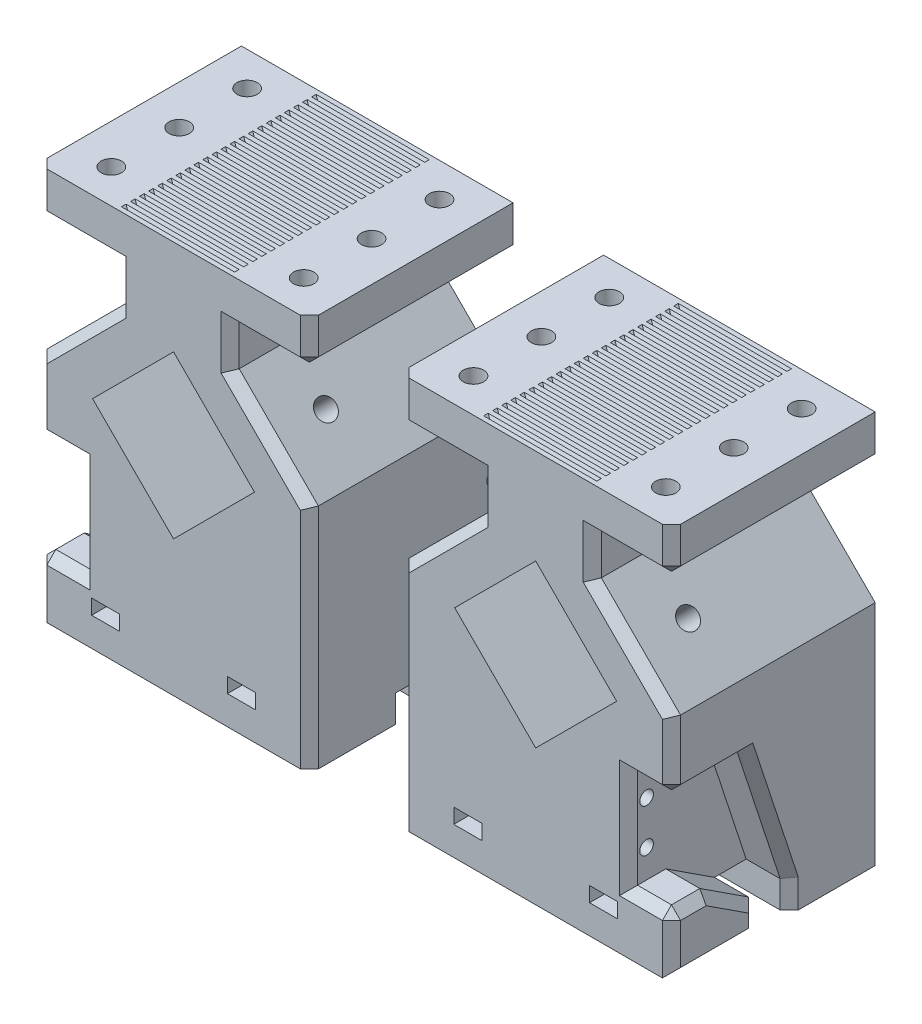
SolidWorks part; units mm, degrees
material "ABS"
ref_plane "Front Plane" through (0, 0, 0) normal (0, 0, 1) x (1, 0, 0)
ref_plane "Top Plane" through (0, 0, 0) normal (0, 1, 0) x (1, 0, 0)
ref_plane "Right Plane" through (0, 0, 0) normal (1, 0, 0) x (0, 0, -1)
sketch "Sketch1" plane through (0, 0, 0) normal (0, 0, 1) x (1, 0, 0)
  line L0 (-30, 25.15) -> (-12.5, 42.65)
  line L2 (30, 25.15) -> (30, -25.15)
  line L3 (30, -25.15) -> (-30, -25.15)
  line L4 (-30, 25.15) -> (-30, -25.15)
  line L5 (30, 25.15) -> (-30, -25.15) construction
  line L6 (30, -25.15) -> (-30, 25.15) construction
  line L7 (30, 25.15) -> (12.5, 42.65)
  line L8 (12.5, 42.65) -> (12.5, 51.65)
  line L9 (-12.5, 42.65) -> (-12.5, 51.65)
  line L10 (-12.5, 51.65) -> (12.5, 51.65) construction
  line L11 (-12.5, 51.65) -> (-30, 51.65)
  line L12 (-30, 51.65) -> (-30, 61.65)
  line L13 (-30, 61.65) -> (30, 61.65)
  line L14 (30, 61.65) -> (30, 51.65)
  line L15 (30, 51.65) -> (12.5, 51.65)
  point P0 (0, 0)
  dimension "D1" = 60
  dimension "D2" = 50.3
  dimension "D3" = 17.5
  dimension "D4" = 17.5
  dimension "D5" = 17.5
  dimension "D6" = 17.5
  dimension "D7" = 9
  dimension "D8" = 10
  dimension "D9" = 25.15
extrude "Boss-Extrude1" add sketch "Sketch1" along normal blind 45
sketch "Sketch2" plane through (0, 0, 45) normal (0, 0, 1) x (1, 0, 0)
  line L0 (0, 40.6296) -> (-17.8898, 22.7398)
  line L1 (-17.8898, 22.7398) -> (0, 4.85)
  line L2 (0, 4.85) -> (17.8898, 22.7398)
  line L3 (17.8898, 22.7398) -> (0, 40.6296)
  line L4 (0, 40.6296) -> (0, 0) construction
  line L5 (-30, -25.15) -> (30, -25.15) construction
  dimension "D1" = 25.3
  dimension "D2" = 25.3
  dimension "D3" = 30
extrude "Cut-Extrude1" cut sketch "Sketch2" against normal blind 25
sketch "Sketch3" plane through (0, -25.15, 0) normal (0, -1, 0) x (1, 0, 0)
  line L0 (-30, 26) -> (30, 26)
  line L1 (-30, 45) -> (-30, 0) construction
  line L2 (30, 45) -> (30, 0) construction
  line L3 (30, 26) -> (30, 19)
  line L4 (30, 19) -> (4.5, 19)
  line L5 (4.5, 19) -> (4.5, 3)
  line L6 (4.5, 3) -> (-4.5, 3)
  line L7 (-4.5, 3) -> (-4.5, 19)
  line L8 (-4.5, 19) -> (-30, 19)
  line L9 (-30, 19) -> (-30, 26)
  line L10 (0, 0) -> (0, 45) construction
  line L11 (-30, 0) -> (30, 0) construction
  line L12 (-30, 45) -> (30, 45) construction
  point P17 (0, 3)
  dimension "D1" = 9
  dimension "D2" = 7
  dimension "D3" = 16
  dimension "D4" = 19
extrude "Cut-Extrude2" cut sketch "Sketch3" against normal blind 6
sketch "Sketch4" plane through (-30, 0, 0) normal (-1, 0, 0) x (0, 0, 1)
  line L0 (45, 25.15) -> (45, -25.15) construction
  line L1 (45, 9.85) -> (28.5, 9.85)
  line L2 (45, 9.85) -> (45, -12.15)
  line L3 (45, -12.15) -> (36.75, -12.15)
  line L5 (45, -25.15) -> (26, -25.15) construction
  line L6 (26, -19.15) -> (36.75, -12.15)
  line L7 (19, -19.15) -> (28.5, 9.85)
  line L8 (26, -19.15) -> (19, -19.15)
  dimension "D1" = 16.5
  dimension "D2" = 13
  dimension "D3" = 22
  dimension "D4" = 8.25
extrude "Cut-Extrude4" cut sketch "Sketch4" against normal blind 9.5
sketch "Sketch5" plane through (0, 0, 0) normal (1, 0, 0) x (0, 0, -1)
  line L0 (-3, -19.15) -> (-3, 9.5665)
  line L1 (-4.0851, 13.008) -> (-11.2085, 23.1813)
  line L2 (-16.1234, 25.7398) -> (-20, 25.7398)
  line L3 (-20, 40.6296) -> (-20, 22.7398) construction
  line L4 (-20, 25.7398) -> (-20, 19.7398)
  line L5 (-20, 22.7398) -> (-20, 4.85) construction
  line L6 (-20, 19.7398) -> (-19.2468, 19.7398)
  line L7 (-14.3319, 17.1813) -> (-10.0851, 11.1162)
  line L8 (-9, 7.6747) -> (-9, -19.15)
  line L9 (-19, -19.15) -> (-3, -19.15) construction
  line L10 (-9, -19.15) -> (-3, -19.15)
  line L11 (-20, 22.7398) -> (-45, 22.7398) construction
  arc A0 (-3, 9.5665) -> (-4.0851, 13.008) centre (-9, 9.5665) ccw
  arc A1 (-10.0851, 11.1162) -> (-9, 7.6747) centre (-15, 7.6747) cw
  arc A2 (-11.2085, 23.1813) -> (-16.1234, 25.7398) centre (-16.1234, 19.7398) ccw
  arc A3 (-19.2468, 19.7398) -> (-14.3319, 17.1813) centre (-19.2468, 13.7398) cw
  point P15 (-19.6234, 19.7398)
  point P24 (-13, 25.7398)
  dimension "D7" = 6
  dimension "D1" = 6
  dimension "D2" = 6
  dimension "D3" = 6
  dimension "D4" = 3
  dimension "D5" = 145
  dimension "D6" = 7
extrude "Cut-Extrude5" cut sketch "Sketch5" against normal mid plane 9
fillet "Fillet1" radius 6 1 edges at (0, -19.15, 9)
ref_plane "Plane1" through (11.5, 0, 0) normal (1, 0, 0) x (0, 0, -1)
sketch "Sketch7" plane through (11.5, 0, 0) normal (1, 0, 0) x (0, 0, -1)
  line L0 (-1, 61.65) -> (-2, 61.65)
  line L1 (-45, 61.65) -> (0, 61.65) construction
  line L2 (-2, 61.65) -> (-1.5, 60.65)
  line L3 (-1.5, 60.65) -> (-1, 61.65)
  line L4 (-1.5, 60.65) -> (-1.5, 61.65) construction
  line L5 (-4, 61.65) -> (-3.5, 60.65)
  line L6 (-3, 61.65) -> (-4, 61.65)
  line L7 (-3.5, 60.65) -> (-3, 61.65)
  line L8 (-6, 61.65) -> (-5.5, 60.65)
  line L9 (-5, 61.65) -> (-6, 61.65)
  line L10 (-5.5, 60.65) -> (-5, 61.65)
  line L11 (-8, 61.65) -> (-7.5, 60.65)
  line L12 (-7, 61.65) -> (-8, 61.65)
  line L13 (-7.5, 60.65) -> (-7, 61.65)
  line L14 (-10, 61.65) -> (-9.5, 60.65)
  line L15 (-9, 61.65) -> (-10, 61.65)
  line L16 (-9.5, 60.65) -> (-9, 61.65)
  line L17 (-12, 61.65) -> (-11.5, 60.65)
  line L18 (-11, 61.65) -> (-12, 61.65)
  line L19 (-11.5, 60.65) -> (-11, 61.65)
  line L20 (-14, 61.65) -> (-13.5, 60.65)
  line L21 (-13, 61.65) -> (-14, 61.65)
  line L22 (-13.5, 60.65) -> (-13, 61.65)
  line L23 (-16, 61.65) -> (-15.5, 60.65)
  line L24 (-15, 61.65) -> (-16, 61.65)
  line L25 (-15.5, 60.65) -> (-15, 61.65)
  line L26 (-18, 61.65) -> (-17.5, 60.65)
  line L27 (-17, 61.65) -> (-18, 61.65)
  line L28 (-17.5, 60.65) -> (-17, 61.65)
  line L29 (-20, 61.65) -> (-19.5, 60.65)
  line L30 (-19, 61.65) -> (-20, 61.65)
  line L31 (-19.5, 60.65) -> (-19, 61.65)
  line L32 (-22, 61.65) -> (-21.5, 60.65)
  line L33 (-21, 61.65) -> (-22, 61.65)
  line L34 (-21.5, 60.65) -> (-21, 61.65)
  line L35 (-24, 61.65) -> (-23.5, 60.65)
  line L36 (-23, 61.65) -> (-24, 61.65)
  line L37 (-23.5, 60.65) -> (-23, 61.65)
  line L38 (-26, 61.65) -> (-25.5, 60.65)
  line L39 (-25, 61.65) -> (-26, 61.65)
  line L40 (-25.5, 60.65) -> (-25, 61.65)
  line L41 (-28, 61.65) -> (-27.5, 60.65)
  line L42 (-27, 61.65) -> (-28, 61.65)
  line L43 (-27.5, 60.65) -> (-27, 61.65)
  line L44 (-30, 61.65) -> (-29.5, 60.65)
  line L45 (-29, 61.65) -> (-30, 61.65)
  line L46 (-29.5, 60.65) -> (-29, 61.65)
  line L47 (-32, 61.65) -> (-31.5, 60.65)
  line L48 (-31, 61.65) -> (-32, 61.65)
  line L49 (-31.5, 60.65) -> (-31, 61.65)
  line L50 (-34, 61.65) -> (-33.5, 60.65)
  line L51 (-33, 61.65) -> (-34, 61.65)
  line L52 (-33.5, 60.65) -> (-33, 61.65)
  line L53 (-36, 61.65) -> (-35.5, 60.65)
  line L54 (-35, 61.65) -> (-36, 61.65)
  line L55 (-35.5, 60.65) -> (-35, 61.65)
  line L56 (-38, 61.65) -> (-37.5, 60.65)
  line L57 (-37, 61.65) -> (-38, 61.65)
  line L58 (-37.5, 60.65) -> (-37, 61.65)
  line L59 (-40, 61.65) -> (-39.5, 60.65)
  line L60 (-39, 61.65) -> (-40, 61.65)
  line L61 (-39.5, 60.65) -> (-39, 61.65)
  line L62 (-42, 61.65) -> (-41.5, 60.65)
  line L63 (-41, 61.65) -> (-42, 61.65)
  line L64 (-41.5, 60.65) -> (-41, 61.65)
  line L65 (-44, 61.65) -> (-43.5, 60.65)
  line L66 (-43, 61.65) -> (-44, 61.65)
  line L67 (-43.5, 60.65) -> (-43, 61.65)
  dimension "D1" = 1
  dimension "D2" = 1
  dimension "D3" = 1
  dimension "D4" = 22
extrude "Cut-Extrude7" cut sketch "Sketch7" against normal blind 23
chamfer "Chamfer1" distance 1 angle 45 44 edges at (-11.5, 61.65, 43.5) (-11.5, 61.65, 41.5) (-11.5, 61.65, 39.5) (-11.5, 61.65, 37.5) (-11.5, 61.65, 35.5) (-11.5, 61.65, 33.5) (-11.5, 61.65, 31.5) (-11.5, 61.65, 29.5) (-11.5, 61.65, 27.5) (-11.5, 61.65, 25.5) (-11.5, 61.65, 23.5) (-11.5, 61.65, 21.5) (-11.5, 61.65, 19.5) (-11.5, 61.65, 17.5) (-11.5, 61.65, 15.5) (-11.5, 61.65, 13.5) (-11.5, 61.65, 11.5) (-11.5, 61.65, 9.5) (-11.5, 61.65, 7.5) (-11.5, 61.65, 5.5) (-11.5, 61.65, 3.5) (-11.5, 61.65, 1.5) (11.5, 61.65, 43.5) (11.5, 61.65, 41.5) (11.5, 61.65, 39.5) (11.5, 61.65, 37.5) (11.5, 61.65, 35.5) (11.5, 61.65, 33.5) (11.5, 61.65, 31.5) (11.5, 61.65, 29.5) (11.5, 61.65, 27.5) (11.5, 61.65, 25.5) (11.5, 61.65, 23.5) (11.5, 61.65, 21.5) (11.5, 61.65, 19.5) (11.5, 61.65, 17.5) (11.5, 61.65, 15.5) (11.5, 61.65, 13.5) (11.5, 61.65, 11.5) (11.5, 61.65, 9.5) (11.5, 61.65, 7.5) (11.5, 61.65, 5.5) (11.5, 61.65, 3.5) (11.5, 61.65, 1.5)
sketch "Sketch8" plane through (0, 61.65, 0) normal (0, 1, 0) x (1, 0, 0)
  line L0 (0, 0) -> (0, -45) construction
  line L1 (30, -45) -> (-30, -45) construction
  line L3 (21.25, -7.5) -> (-21.25, -7.5) construction
  line L4 (21.25, -7.5) -> (21.25, -37.5) construction
  line L5 (21.25, -37.5) -> (-21.25, -37.5) construction
  line L6 (-21.25, -7.5) -> (-21.25, -37.5) construction
  line L7 (21.25, -7.5) -> (-21.25, -37.5) construction
  line L8 (21.25, -37.5) -> (-21.25, -7.5) construction
  circle A0 centre (-21.25, -37.5) radius 2.25
  circle A1 centre (-21.25, -22.5) radius 2.25
  circle A2 centre (-21.25, -7.5) radius 2.25
  circle A3 centre (21.25, -7.5) radius 2.25
  circle A4 centre (21.25, -22.5) radius 2.25
  circle A5 centre (21.25, -37.5) radius 2.25
  point P5 (0, -22.5)
  dimension "D3" = 4.5
  dimension "D4" = 4.5
  dimension "D5" = 4.5
  dimension "D6" = 4.5
  dimension "D7" = 4.5
  dimension "D8" = 4.5
  dimension "D1" = 30
  dimension "D2" = 42.5
extrude "Cut-Extrude8" cut sketch "Sketch8" against normal blind 10
sketch "Sketch9" plane through (0, 51.65, 0) normal (0, -1, 0) x (1, 0, 0)
  line L1 (-25.2915, 22.5) -> (-23.2707, 19)
  line L2 (-23.2707, 19) -> (-19.2293, 19)
  line L3 (-19.2293, 19) -> (-17.2085, 22.5)
  line L4 (-17.2085, 22.5) -> (-19.2293, 26)
  line L5 (-19.2293, 26) -> (-23.2707, 26)
  line L6 (-23.2707, 26) -> (-25.2915, 22.5)
  line L7 (-25.2915, 37.5) -> (-23.2707, 34)
  line L8 (-23.2707, 34) -> (-19.2293, 34)
  line L9 (-19.2293, 34) -> (-17.2085, 37.5)
  line L10 (-17.2085, 37.5) -> (-19.2293, 41)
  line L11 (-19.2293, 41) -> (-23.2707, 41)
  line L12 (-23.2707, 41) -> (-25.2915, 37.5)
  line L13 (-25.2915, 7.5) -> (-23.2707, 4)
  line L14 (-23.2707, 4) -> (-19.2293, 4)
  line L15 (-19.2293, 4) -> (-17.2085, 7.5)
  line L16 (-17.2085, 7.5) -> (-19.2293, 11)
  line L17 (-19.2293, 11) -> (-23.2707, 11)
  line L18 (-23.2707, 11) -> (-25.2915, 7.5)
  line L19 (25.2915, 7.5) -> (23.2707, 11)
  line L20 (23.2707, 11) -> (19.2293, 11)
  line L21 (19.2293, 11) -> (17.2085, 7.5)
  line L22 (17.2085, 7.5) -> (19.2293, 4)
  line L23 (19.2293, 4) -> (23.2707, 4)
  line L24 (23.2707, 4) -> (25.2915, 7.5)
  line L25 (25.4834, 22.6108) -> (23.4627, 26.1108)
  line L26 (23.4627, 26.1108) -> (19.4212, 26.1108)
  line L27 (19.4212, 26.1108) -> (17.4005, 22.6108)
  line L28 (17.4005, 22.6108) -> (19.4212, 19.1108)
  line L29 (19.4212, 19.1108) -> (23.4627, 19.1108)
  line L30 (23.4627, 19.1108) -> (25.4834, 22.6108)
  line L31 (25.4834, 37.6108) -> (23.4627, 41.1108)
  line L32 (23.4627, 41.1108) -> (19.4212, 41.1108)
  line L33 (19.4212, 41.1108) -> (17.4005, 37.6108)
  line L34 (17.4005, 37.6108) -> (19.4212, 34.1108)
  line L35 (19.4212, 34.1108) -> (23.4627, 34.1108)
  line L36 (23.4627, 34.1108) -> (25.4834, 37.6108)
  circle A0 centre (-21.25, 22.5) radius 3.5 construction
  circle A1 centre (-21.25, 37.5) radius 3.5 construction
  circle A2 centre (-21.25, 7.5) radius 3.5 construction
  circle A3 centre (21.25, 7.5) radius 3.5 construction
  circle A4 centre (21.4419, 22.6108) radius 3.5 construction
  circle A5 centre (21.4419, 37.6108) radius 3.5 construction
  dimension "D1" = 7
  dimension "D2" = 7
  dimension "D3" = 7
  dimension "D4" = 7
  dimension "D5" = 7
  dimension "D6" = 7
extrude "Cut-Extrude9" cut sketch "Sketch9" against normal blind 3.2
sketch "Sketch10" plane through (0, -25.15, 0) normal (0, -1, 0) x (1, 0, 0)
  line L0 (-30, 45) -> (-30, 26) construction
  line L1 (15, 7.5) -> (-15, 7.5) construction
  line L2 (15, 7.5) -> (15, 37.5) construction
  line L3 (15, 37.5) -> (-15, 37.5) construction
  line L4 (-15, 7.5) -> (-15, 37.5) construction
  line L5 (15, 7.5) -> (-15, 37.5) construction
  line L6 (15, 37.5) -> (-15, 7.5) construction
  line L7 (-30, 45) -> (30, 45) construction
  circle A0 centre (-15, 37.5) radius 1.75
  circle A1 centre (-15, 7.5) radius 1.75
  circle A2 centre (15, 7.5) radius 1.75
  circle A3 centre (15, 37.5) radius 1.75
  point P0 (0, 22.5)
  dimension "D5" = 3.5
  dimension "D6" = 3.5
  dimension "D7" = 3.5
  dimension "D8" = 3.5
  dimension "D1" = 30
  dimension "D2" = 22.5
  dimension "D3" = 30
  dimension "D4" = 30
extrude "Cut-Extrude10" cut sketch "Sketch10" against normal blind 20
ref_plane "Plane2" through (0, -18.8, 0) normal (0, -1, 0) x (-1, 0, 0)
sketch "Sketch11" plane through (0, -18.8, 0) normal (0, -1, 0) x (-1, 0, 0)
  line L0 (30, -45) -> (-30, -45) construction
  line L1 (-11.9, -45) -> (-18.1, -45)
  line L2 (-11.9, -45) -> (-11.9, -33)
  line L3 (-11.9, -33) -> (-18.1, -33)
  line L4 (-18.1, -45) -> (-18.1, -33)
  line L5 (30, 0) -> (-30, 0) construction
  line L6 (11.9, -45) -> (18.1, -45)
  line L7 (11.9, -45) -> (11.9, -33)
  line L8 (11.9, -33) -> (18.1, -33)
  line L9 (18.1, -45) -> (18.1, -33)
  line L10 (11.9, 0) -> (18.1, 0)
  line L11 (11.9, 0) -> (11.9, -12)
  line L12 (11.9, -12) -> (18.1, -12)
  line L13 (18.1, 0) -> (18.1, -12)
  line L14 (-30, -45) -> (-30, -26) construction
  line L15 (-18.1, 0) -> (-11.9, 0)
  line L16 (-18.1, 0) -> (-18.1, -12)
  line L17 (-18.1, -12) -> (-11.9, -12)
  line L18 (-11.9, 0) -> (-11.9, -12)
  line L19 (30, -45) -> (30, -26) construction
  dimension "D1" = 11.9
  dimension "D2" = 6.2
  dimension "D3" = 12
  dimension "D4" = 11.9
  dimension "D5" = 6.2
  dimension "D6" = 12
extrude "Cut-Extrude11" cut sketch "Sketch11" against normal blind 3.3
sketch "Sketch12" plane through (0, -18.8, 0) normal (0, -1, 0) x (-1, 0, 0)
  line L0 (-15, -7.5) -> (-15, -4.0359) construction
  line L1 (15, -34.0359) -> (12, -35.7679)
  line L2 (12, -35.7679) -> (12, -39.2321)
  line L3 (12, -39.2321) -> (15, -40.9641)
  line L4 (15, -40.9641) -> (18, -39.2321)
  line L5 (18, -39.2321) -> (18, -35.7679)
  line L6 (18, -35.7679) -> (15, -34.0359)
  line L7 (15, -10.9641) -> (18, -9.2321)
  line L8 (18, -9.2321) -> (18, -5.7679)
  line L9 (18, -5.7679) -> (15, -4.0359)
  line L10 (15, -4.0359) -> (12, -5.7679)
  line L11 (12, -5.7679) -> (12, -9.2321)
  line L12 (12, -9.2321) -> (15, -10.9641)
  line L13 (-15, -10.9641) -> (-12, -9.2321)
  line L14 (-12, -9.2321) -> (-12, -5.7679)
  line L15 (-12, -5.7679) -> (-15, -4.0359)
  line L16 (-15, -4.0359) -> (-18, -5.7679)
  line L17 (-18, -5.7679) -> (-18, -9.2321)
  line L18 (-18, -9.2321) -> (-15, -10.9641)
  line L19 (-15, -34.0359) -> (-18, -35.7679)
  line L20 (-18, -35.7679) -> (-18, -39.2321)
  line L21 (-18, -39.2321) -> (-15, -40.9641)
  line L22 (-15, -40.9641) -> (-12, -39.2321)
  line L23 (-12, -39.2321) -> (-12, -35.7679)
  line L24 (-12, -35.7679) -> (-15, -34.0359)
  line L25 (15, -7.5) -> (15, -4.0359) construction
  line L26 (-15, -37.5) -> (-15, -34.0359) construction
  line L27 (15, -37.5) -> (15, -34.0359) construction
  circle A0 centre (15, -37.5) radius 3 construction
  circle A1 centre (15, -7.5) radius 3 construction
  circle A2 centre (-15, -7.5) radius 3 construction
  circle A3 centre (-15, -37.5) radius 3 construction
  dimension "D1" = 6
  dimension "D2" = 6
  dimension "D3" = 6
  dimension "D4" = 6
extrude "Cut-Extrude12" cut sketch "Sketch12" along normal blind 1.5
sketch "Sketch13" plane through (-20.5, 0, 0) normal (-1, 0, 0) x (0, 0, 1)
  line L0 (41, -5.9) -> (41, 3.6) construction
  line L1 (45, -12.15) -> (45, 9.85) construction
  line L2 (36.75, -12.15) -> (45, -12.15) construction
  circle A0 centre (41, -5.9) radius 1.5
  circle A1 centre (41, 3.6) radius 1.5
  dimension "D4" = 3
  dimension "D5" = 3
  dimension "D1" = 4
  dimension "D2" = 9.5
  dimension "D3" = 6.25
extrude "Cut-Extrude13" cut sketch "Sketch13" against normal blind 15
sketch "Sketch14" plane through (-27.575, 27.575, 0) normal (-0.7071, 0.7071, 0) x (0, 0, 1)
  line L0 (45, 21.3193) -> (45, -3.4295) construction
  line L1 (45, -3.4295) -> (0, -3.4295) construction
  circle A0 centre (32.5, 9.0705) radius 2.25
  dimension "D1" = 12.5
  dimension "D2" = 12.5
  dimension "D3" = 4.5
extrude "Cut-Extrude14" cut sketch "Sketch14" against normal blind 15
sketch "Sketch15" plane through (-20.3148, 20.3148, 0) normal (0.7071, -0.7071, 0) x (0, 0, -1)
  line L0 (-32.5, 9.0705) -> (-28.4585, 9.0705) construction
  line L1 (-28.4585, 9.0705) -> (-30.4793, 12.5705)
  line L2 (-30.4793, 12.5705) -> (-34.5207, 12.5705)
  line L3 (-34.5207, 12.5705) -> (-36.5415, 9.0705)
  line L4 (-36.5415, 9.0705) -> (-34.5207, 5.5705)
  line L5 (-34.5207, 5.5705) -> (-30.4793, 5.5705)
  line L6 (-30.4793, 5.5705) -> (-28.4585, 9.0705)
  circle A0 centre (-32.5, 9.0705) radius 3.5 construction
  dimension "D1" = 7
extrude "Cut-Extrude15" cut sketch "Sketch15" against normal blind 3.5
mirror "Mirror1" about plane through (0, 0, 0) normal (1, 0, 0) of "Cut-Extrude14", "Cut-Extrude15"
sketch "Sketch16" plane through (30, 0, 0) normal (1, 0, 0) x (0, 0, -1)
  line L0 (-4, 11.25) -> (-4, -11.25) construction
  line L1 (-19, -25.15) -> (0, -25.15) construction
  line L2 (0, -25.15) -> (0, 25.15) construction
  circle A0 centre (-4, 11.25) radius 1.8
  circle A1 centre (-4, -11.25) radius 1.8
  dimension "D4" = 3.6
  dimension "D5" = 3.6
  dimension "D1" = 13.9
  dimension "D2" = 22.5
  dimension "D3" = 4
extrude "Cut-Extrude23" cut sketch "Sketch16" against normal blind 20
sketch "Sketch17" plane through (0, 0, 0) normal (0, 0, -1) x (-1, 0, 0)
  line L0 (30, -25.15) -> (-30, -25.15) construction
  line L1 (-23.65, -8.15) -> (-20.35, -8.15)
  line L2 (-23.65, -8.15) -> (-23.65, -14.35)
  line L3 (-23.65, -14.35) -> (-20.35, -14.35)
  line L4 (-20.35, -8.15) -> (-20.35, -14.35)
  line L5 (-23.65, 14.35) -> (-20.35, 14.35)
  line L6 (-23.65, 14.35) -> (-23.65, 8.15)
  line L7 (-23.65, 8.15) -> (-20.35, 8.15)
  line L8 (-20.35, 14.35) -> (-20.35, 8.15)
  line L9 (-30, -25.15) -> (-30, 25.15) construction
  point P12 (-22, -8.15)
  dimension "D1" = 10.8
  dimension "D2" = 6.35
  dimension "D3" = 6.2
  dimension "D4" = 6.2
  dimension "D5" = 3.3
  dimension "D6" = 16.3
extrude "Cut-Extrude24" cut sketch "Sketch17" against normal blind 8
sketch "Sketch18" plane through (23.65, 0, 0) normal (-1, 0, 0) x (0, 0, 1)
  line L0 (0.8246, -11.25) -> (4.1512, -11.25) construction
  line L1 (0.8246, 11.25) -> (2.4123, 8.5)
  line L2 (2.4123, 8.5) -> (5.5877, 8.5)
  line L3 (5.5877, 8.5) -> (7.1754, 11.25)
  line L4 (7.1754, 11.25) -> (5.5877, 14)
  line L5 (5.5877, 14) -> (2.4123, 14)
  line L6 (2.4123, 14) -> (0.8246, 11.25)
  line L7 (0.8246, -11.25) -> (2.4123, -14)
  line L8 (2.4123, -14) -> (5.5877, -14)
  line L9 (5.5877, -14) -> (7.1754, -11.25)
  line L10 (7.1754, -11.25) -> (5.5877, -8.5)
  line L11 (5.5877, -8.5) -> (2.4123, -8.5)
  line L12 (2.4123, -8.5) -> (0.8246, -11.25)
  line L13 (4, 11.25) -> (1.0281, 11.25) construction
  circle A0 centre (4, 11.25) radius 2.75 construction
  circle A1 centre (4, -11.25) radius 2.75 construction
  dimension "D1" = 5.5
  dimension "D2" = 5.5
extrude "Cut-Extrude25" cut sketch "Sketch18" against normal blind 1.5
chamfer "Chamfer2" distance 2 angle 45 23 edges at (-30, -25.15, 35.5) (-30, -22.15, 26) (-30, -15.65, 31.375) (-30, -12.15, 40.875) (-30, -18.65, 45) (-30, -22.15, 19) (-30, -4.65, 23.75) (-30, 9.85, 36.75) (-25.25, -12.15, 45) (-20.5, -1.15, 45) (-25.25, 9.85, 45) (-30, 17.5, 45) (-30, 51.65, 22.5) (-21.25, 33.9, 45) (-12.5, 47.15, 45) (-21.25, 51.65, 45) (-30, 56.65, 45) (30, 0, 45) (21.25, 33.9, 45) (12.5, 47.15, 45) (21.25, 51.65, 45) (30, 56.65, 45) (30, 51.65, 22.5)
ref_plane "Plane3" through (40, 0, 0) normal (1, 0, 0) x (0, 0, -1)
mirror "Mirror4" about plane through (40, 0, 0) normal (1, 0, 0) of bodies 119
